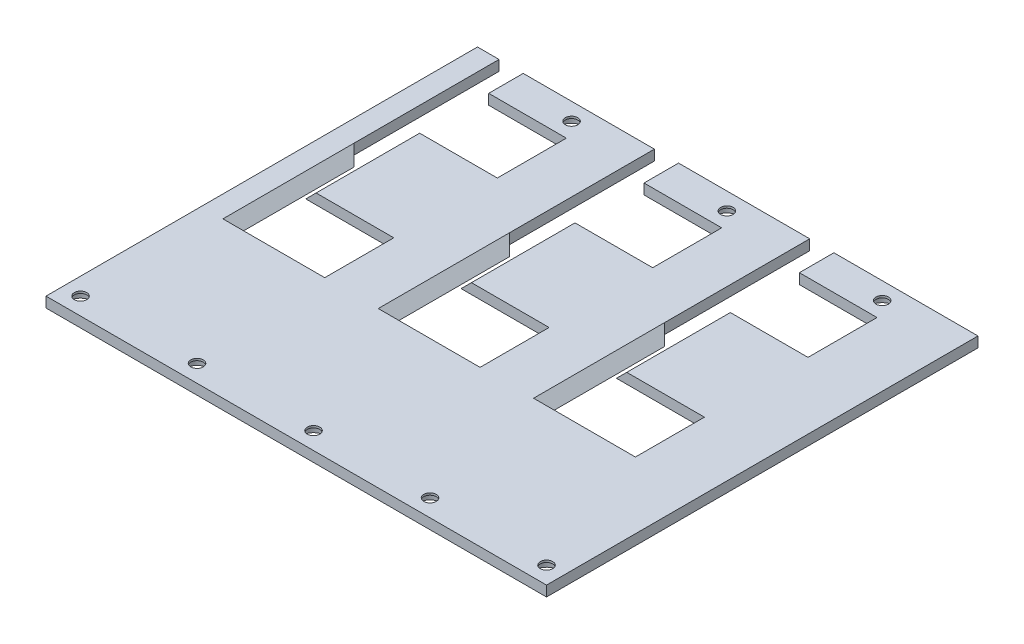
SolidWorks part; units mm, degrees
ref_plane "Płaszczyzna przednia" through (0, 0, 0) normal (0, 0, 1) x (1, 0, 0)
ref_plane "Płaszczyzna górna" through (0, 0, 0) normal (0, 1, 0) x (1, 0, 0)
ref_plane "Płaszczyzna prawa" through (0, 0, 0) normal (1, 0, 0) x (0, 0, -1)
sketch "Szkic1" plane through (0, 0, 0) normal (0, 1, 0) x (1, 0, 0)
  line L1 (-72.5, -62.5) -> (72.5, -62.5)
  line L2 (-72.5, -62.5) -> (-72.5, 62.5)
  line L3 (-72.5, 62.5) -> (72.5, 62.5)
  line L4 (72.5, -62.5) -> (72.5, 62.5)
  line L5 (0, 62.5) -> (0, -62.5) construction
  line L6 (-72.5, 0) -> (72.5, 0) construction
  point P0 (0, 0)
  dimension "D1" = 145
  dimension "D2" = 125
extrude "Dodanie-wyciągnięcie1" add sketch "Szkic1" along normal blind 3
sketch "Szkic2" plane through (0, 0, 0) normal (0, -1, 0) x (1, 0, 0)
  line L1 (-39.75, -32.5) -> (-62.25, -32.5)
  line L12 (-39.75, 17.5) -> (-39.75, -2.5)
  line L65 (-39.75, -32.5) -> (-39.75, -52.5)
  line L67 (-72.5, -62.5) -> (-72.5, 62.5) construction
  line L70 (72.5, -62.5) -> (-72.5, -62.5) construction
  line L71 (-59.25, -62.5) -> (-66.25, -62.5)
  line L72 (-72.5, 62.5) -> (72.5, 62.5) construction
  line L202 (-63.25, -17.5) -> (-66.25, -20.5)
  line L203 (-66.25, -20.5) -> (-66.25, -62.5)
  line L205 (-59.25, -62.5) -> (-59.25, -52.5)
  line L208 (-39.75, 17.5) -> (-63.25, 17.5)
  line L218 (-39.75, -2.5) -> (-62.25, -2.5)
  line L224 (-39.75, -52.5) -> (-59.25, -52.5)
  line L229 (-63.25, 17.5) -> (-63.25, -17.5)
  line L231 (-62.25, -2.5) -> (-62.25, -32.5)
  point P10 (-38.1849, 22.5)
  line M16 (-72.5, -62.5) -> (72.5, -62.5)
  dimension "D1" = 50
  dimension "D2" = 20
  dimension "D3" = 1
  dimension "D4" = 23.5
  dimension "D5" = 20
  dimension "D6" = 9.25
  dimension "D7" = 45
  dimension "D10" = 135
  dimension "D12" = 42
  dimension "D13" = 6.25
  dimension "D11" = 7
extrude "Wytnij-wyciągnięcie1" cut sketch "Szkic2" against normal up to next contours L231 L218 L12 L208 L229 L202 L203 L205 L224 L65 L1 M16 region at (-40.5927, 0, -42.5)
chamfer "Sfazowanie1" distance 3 angle 45 4 edges at (-63.25, 3, 0) (-62.25, 3, -17.5) (-39.75, 3, -42.5) (-39.75, 3, 7.5)
pattern_linear "Szyk liniowy1" count 3 spacing 45 along (1, 0, 0) of "Sfazowanie1", "Wytnij-wyciągnięcie1"
sketch "Szkic3" plane through (0, 0, 0) normal (0, -1, 0) x (1, 0, 0)
  line L0 (-72.5, -62.5) -> (-72.5, 62.5) construction
  line L1 (-72.5, 62.5) -> (72.5, 62.5) construction
  line L3 (-21.25, -62.5) -> (-59.25, -62.5) construction
  point P0 (-67.5, 57.5)
  point P5 (-33.75, 57.5)
  point P6 (-40.25, -57.4985)
  point P7 (0, 57.5)
  point P8 (33.75, 57.5)
  point P9 (67.5, 57.5)
  point P10 (4.75, -57.4985)
  point P12 (49.75, -57.4985)
  point P14 (-40.25, -62.5)
  dimension "D1" = 5
  dimension "D2" = 5
  dimension "D4" = 33.75
  dimension "D5" = 5.0015
  dimension "D3" = 5
hole_wizard "Pogłębienie walcowe pod M3 Śrubę z łbem stożkowym ściętym1" positions "Szkic3" profile "Szkic4" counterbore size "M3" standard "DIN"
sketch "Szkic4" plane through (-67.5, 0, 57.5) normal (1, 0, 0) x (0, 0, -1)
  line L0 (0, 0) -> (0, 7.7815)
  line L1 (0, 7.7815) -> (1.8, 6.7)
  line L2 (1.8, 6.7) -> (1.8, 2.4)
  line L3 (1.8, 2.4) -> (3.5, 2.4)
  line L4 (3.5, 2.4) -> (3.5, 0)
  line L5 (3.5, 0) -> (0, 0)
  line L10 (0, 7.7815) -> (-1.8, 6.7) construction
  line L11 (0, -6.35) -> (0, 107.95) construction
  dimension "Średnica otworu" = 3.6
  dimension "Głębokość otworu" = 6.7
  dimension "Średnica pogłębienia walcowego" = 7
  dimension "Głębokość pogłębienia walcowego" = 2.4
  dimension "Kąt wiertła" = 118
